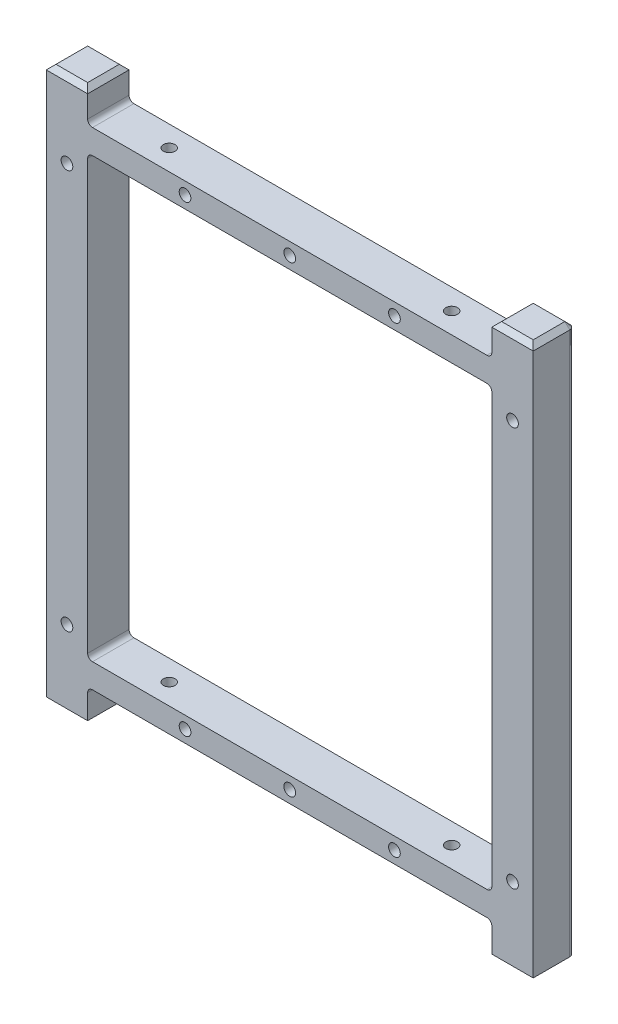
SolidWorks part; units mm, degrees
material "6061 Alloy"
ref_plane "Frontal" through (0, 0, 0) normal (0, 0, 1) x (1, 0, 0)
ref_plane "Superior" through (0, 0, 0) normal (0, 1, 0) x (1, 0, 0)
ref_plane "Direito" through (0, 0, 0) normal (1, 0, 0) x (0, 0, -1)
sketch "Sketch1" plane through (0, 0, 0) normal (0, 0, 1) x (1, 0, 0)
  line L1 (-50, -56.75) -> (50, -56.75)
  line L2 (-50, -56.75) -> (-50, 56.75)
  line L3 (-50, 56.75) -> (50, 56.75)
  line L4 (50, -56.75) -> (50, 56.75)
  line L5 (-50, -56.75) -> (50, 56.75) construction
  line L6 (-50, 56.75) -> (50, -56.75) construction
  point P0 (0, 0)
  dimension "D1" = 113.5
  dimension "D2" = 100
extrude "Boss-Extrude1" add sketch "Sketch1" along normal mid plane 8.5
sketch "Sketch4" plane through (0, 0, 4.25) normal (0, 0, 1) x (1, 0, 0)
  line L0 (-50, 56.75) -> (-50, -56.75) construction
  line L1 (-40.5, -44.75) -> (40.5, -44.75)
  line L2 (-41.5, -43.75) -> (-41.5, 44.25)
  line L3 (-40.5, 45.25) -> (40.5, 45.25)
  line L4 (41.5, -43.75) -> (41.5, 44.25)
  line L5 (-40.5, -43.75) -> (40.5, 44.25) construction
  line L6 (-40.5, 44.25) -> (40.5, -43.75) construction
  line L7 (50, 56.75) -> (-50, 56.75) construction
  line L8 (-41.5, 56.75) -> (41.5, 56.75)
  line L9 (-41.5, 56.75) -> (-41.5, 51.25)
  line L10 (-40.5, 50.25) -> (40.5, 50.25)
  line L11 (41.5, 56.75) -> (41.5, 51.25)
  line L12 (-50, -56.75) -> (50, -56.75) construction
  line L13 (-41.5, -56.75) -> (41.5, -56.75)
  line L14 (-41.5, -56.75) -> (-41.5, -50.75)
  line L15 (-40.5, -49.75) -> (40.5, -49.75)
  line L16 (41.5, -56.75) -> (41.5, -50.75)
  line L17 (50, -56.75) -> (50, 56.75) construction
  arc A0 (-41.5, 51.25) -> (-40.5, 50.25) centre (-40.5, 51.25) ccw
  arc A1 (40.5, 50.25) -> (41.5, 51.25) centre (40.5, 51.25) ccw
  arc A2 (-40.5, 45.25) -> (-41.5, 44.25) centre (-40.5, 44.25) ccw
  arc A3 (40.5, 45.25) -> (41.5, 44.25) centre (40.5, 44.25) cw
  arc A4 (41.5, -43.75) -> (40.5, -44.75) centre (40.5, -43.75) cw
  arc A5 (-40.5, -44.75) -> (-41.5, -43.75) centre (-40.5, -43.75) cw
  arc A6 (-40.5, -49.75) -> (-41.5, -50.75) centre (-40.5, -50.75) ccw
  arc A7 (40.5, -49.75) -> (41.5, -50.75) centre (40.5, -50.75) cw
  point P0 (1.8681, -1.8902)
  dimension "D11" = 1
  dimension "D12" = 1
  dimension "D13" = 1
  dimension "D14" = 1
  dimension "D15" = 1
  dimension "D16" = 1
  dimension "D17" = 1
  dimension "D18" = 1
  dimension "D1" = 8.5
  dimension "D2" = 8.5
  dimension "D3" = 8.5
  dimension "D4" = 6.5
  dimension "D5" = 8.5
  dimension "D6" = 8.5
  dimension "D7" = 7
  dimension "D8" = 5
  dimension "D9" = 5
  dimension "D10" = 8.5
extrude "Cut-Extrude1" cut sketch "Sketch4" against normal through all
hole_wizard "M2 Hole1-C" positions "Sketch6" profile "Sketch5" hole size "M2" standard "DIN"
sketch "Sketch6" plane through (0, 0, 4.25) normal (0, 0, 1) x (1, 0, 0)
  line L0 (-50, 56.75) -> (-50, -56.75) construction
  line L1 (50, -56.75) -> (50, 56.75) construction
  line L2 (-40.5, 50.25) -> (40.5, 50.25) construction
  line L3 (40.5, -49.75) -> (-40.5, -49.75) construction
  point P0 (-45.75, -40.75)
  point P2 (45.75, -40.75)
  point P4 (-45.75, 41.25)
  point P6 (45.75, 41.25)
  dimension "D1" = 4.25
  dimension "D2" = 4.25
  dimension "D3" = 9
  dimension "D4" = 9
sketch "Sketch5" plane through (-45.75, -40.75, 4.25) normal (1, 0, 0) x (0, -1, 0)
  line L0 (0, 0) -> (0, 3.721)
  line L1 (0, 3.721) -> (1.2, 3)
  line L2 (1.2, 3) -> (1.2, 0)
  line L5 (1.2, 0) -> (0, 0)
  line L10 (0, 3.721) -> (-1.2, 3) construction
  line L11 (0, -6.35) -> (0, 107.95) construction
  dimension "Hole Dia." = 2.4
  dimension "Hole Depth" = 3
  dimension "Drill Angle" = 118
hole_wizard "M2 Hole2-D" positions "Sketch19" profile "Sketch18" countersink size "M2" standard "DIN" end condition through all
sketch "Sketch19" plane through (0, 0, -4.25) normal (0, 0, -1) x (-1, 0, 0)
  line L0 (-41.5, 51.25) -> (-41.5, 56.75) construction
  line L1 (41.5, 56.75) -> (41.5, 51.25) construction
  line L2 (40.5, 50.25) -> (-40.5, 50.25) construction
  line L3 (-40.5, -49.75) -> (40.5, -49.75) construction
  point P0 (-21.5, 47.75)
  point P2 (21.5, 47.75)
  point P4 (-21.5, -47.25)
  point P6 (21.5, -47.25)
  dimension "D1" = 20
  dimension "D2" = 20
  dimension "D3" = 2.5
  dimension "D4" = 2.5
sketch "Sketch18" plane through (21.5, 47.75, -4.25) normal (1, 0, 0) x (0, 1, 0)
  line L0 (0, 0) -> (0, 8.5)
  line L1 (0, 8.5) -> (1.2, 8.5)
  line L2 (1.2, 8.5) -> (1.2, 1)
  line L3 (1.2, 1) -> (2.2, 0)
  line L5 (2.2, 0) -> (0, 0)
  line L6 (-1.2, 1) -> (-2.2, 0) construction
  line L11 (0, -6.35) -> (0, 107.95) construction
  dimension "Thru Hole Dia." = 2.4
  dimension "Thru Hole Depth" = 8.5
  dimension "Near C'Sink Dia." = 4.4
  dimension "Near C'Sink Angle" = 90
hole_wizard "M2 Hole3-E" positions "Sketch13" profile "Sketch12" hole size "M2" standard "DIN"
sketch "Sketch13" plane through (0, 0, 4.25) normal (0, 0, 1) x (1, 0, 0)
  line L0 (40.5, -49.75) -> (-40.5, -49.75) construction
  line L1 (-40.5, 50.25) -> (40.5, 50.25) construction
  point P0 (0, 47.75)
  point P2 (0, -47.25)
  dimension "D1" = 2.5
  dimension "D2" = 2.5
sketch "Sketch12" plane through (0, 47.75, 4.25) normal (1, 0, 0) x (0, -1, 0)
  line L0 (0, 0) -> (0, 4.721)
  line L1 (0, 4.721) -> (1.2, 4)
  line L2 (1.2, 4) -> (1.2, 0)
  line L5 (1.2, 0) -> (0, 0)
  line L10 (0, 4.721) -> (-1.2, 4) construction
  line L11 (0, -6.35) -> (0, 107.95) construction
  dimension "Hole Dia." = 2.4
  dimension "Hole Depth" = 4
  dimension "Drill Angle" = 118
hole_wizard "M2 Hole4-F" positions "Sketch23" profile "Sketch22" hole size "M2" standard "DIN"
sketch "Sketch23" plane through (0, 50.25, 0) normal (0, 1, 0) x (1, 0, 0)
  line L0 (-40.5, 4.25) -> (40.5, 4.25) construction
  line L1 (-41.5, 4.25) -> (-41.5, -4.25) construction
  line L2 (41.5, 4.25) -> (41.5, -4.25) construction
  point P0 (-29, 0)
  point P2 (29, 0)
  dimension "D1" = 4.25
  dimension "D2" = 12.5
  dimension "D3" = 12.5
sketch "Sketch22" plane through (-29, 50.25, 0) normal (1, 0, 0) x (0, 0, 1)
  line L0 (0, 0) -> (0, 10.721)
  line L1 (0, 10.721) -> (1.2, 10)
  line L2 (1.2, 10) -> (1.2, 0)
  line L5 (1.2, 0) -> (0, 0)
  line L10 (0, 10.721) -> (-1.2, 10) construction
  line L11 (0, -6.35) -> (0, 107.95) construction
  dimension "Hole Dia." = 2.4
  dimension "Hole Depth" = 10
  dimension "Drill Angle" = 118
hole_wizard "M2 Hole5-G" positions "Sketch17" profile "Sketch16" hole size "M2" standard "DIN"
sketch "Sketch17" plane through (0, -49.75, 0) normal (0, -1, 0) x (-1, 0, 0)
  line L0 (41.5, 4.25) -> (41.5, -4.25) construction
  line L1 (-41.5, 4.25) -> (-41.5, -4.25) construction
  line L2 (-40.5, -4.25) -> (40.5, -4.25) construction
  point P0 (29, 0)
  point P2 (-29, 0)
  dimension "D1" = 12.5
  dimension "D2" = 12.5
  dimension "D3" = 4.25
sketch "Sketch16" plane through (-29, -49.75, 0) normal (1, 0, 0) x (0, 0, -1)
  line L0 (0, 0) -> (0, 10.721)
  line L1 (0, 10.721) -> (1.2, 10)
  line L2 (1.2, 10) -> (1.2, 0)
  line L5 (1.2, 0) -> (0, 0)
  line L10 (0, 10.721) -> (-1.2, 10) construction
  line L11 (0, -6.35) -> (0, 107.95) construction
  dimension "Hole Dia." = 2.4
  dimension "Hole Depth" = 10
  dimension "Drill Angle" = 118
hole_wizard "M2 Hole6-H" positions "Sketch21" profile "Sketch20" hole size "M2" standard "DIN"
sketch "Sketch21" plane through (0, 0, -4.25) normal (0, 0, -1) x (-1, 0, 0)
  line L0 (40.5, 50.25) -> (-40.5, 50.25) construction
  line L1 (-41.5, 51.25) -> (-41.5, 56.75) construction
  line L2 (41.5, 56.75) -> (41.5, 51.25) construction
  line L3 (-40.5, -49.75) -> (40.5, -49.75) construction
  point P0 (-35.5, 47.75)
  point P2 (35.5, 47.75)
  point P4 (-35.5, -47.25)
  point P6 (35.5, -47.25)
  dimension "D1" = 2.5
  dimension "D2" = 6
  dimension "D3" = 6
  dimension "D4" = 2.5
sketch "Sketch20" plane through (35.5, 47.75, -4.25) normal (1, 0, 0) x (0, 1, 0)
  line L0 (0, 0) -> (0, 5.721)
  line L1 (0, 5.721) -> (1.2, 5)
  line L2 (1.2, 5) -> (1.2, 0)
  line L5 (1.2, 0) -> (0, 0)
  line L10 (0, 5.721) -> (-1.2, 5) construction
  line L11 (0, -6.35) -> (0, 107.95) construction
  dimension "Hole Dia." = 2.4
  dimension "Hole Depth" = 5
  dimension "Drill Angle" = 118
fillet "Fillet1" radius 1 2 edges at (-50, 0, -4.25) (50, 0, -4.25)
chamfer "Chamfer1" distance 1 angle 45 20 edges at (-41.5, -56.75, 0) (-45.75, -56.75, 4.25) (-50, -56.75, 0.5) (-49.7071, -56.75, -3.9571) (-45.25, -56.75, -4.25) (-45.75, 56.75, 4.25) (-50, 56.75, 0.5) (-49.7071, 56.75, -3.9571) (-45.25, 56.75, -4.25) (-41.5, 56.75, 0) (45.75, -56.75, 4.25) (41.5, -56.75, 0) (45.25, -56.75, -4.25) (49.7071, -56.75, -3.9571) (50, -56.75, 0.5) (49.7071, 56.75, -3.9571) (50, 56.75, 0.5) (45.75, 56.75, 4.25) (41.5, 56.75, 0) (45.25, 56.75, -4.25)
